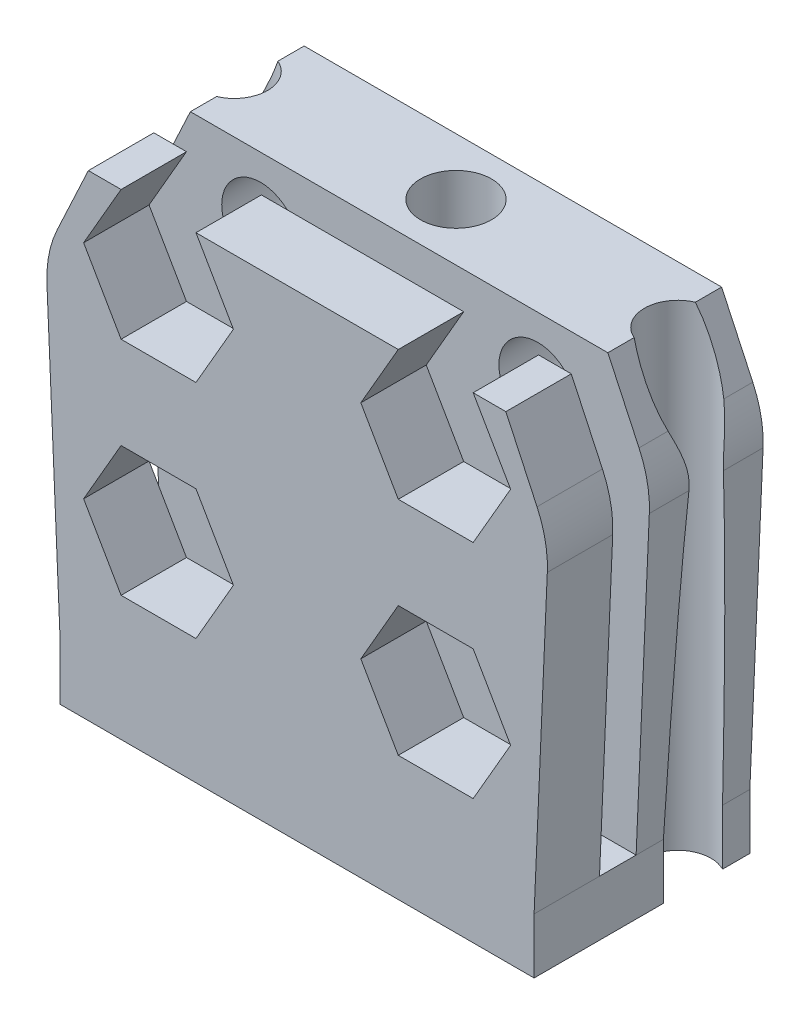
SolidWorks part; units mm, degrees
ref_plane "Front Plane" through (0, 0, 0) normal (0, 0, 1) x (1, 0, 0)
ref_plane "Top Plane" through (0, 0, 0) normal (0, 1, 0) x (1, 0, 0)
ref_plane "Right Plane" through (0, 0, 0) normal (1, 0, 0) x (0, 0, -1)
sketch "Sketch1" plane through (0, 0, 0) normal (0, 0, 1) x (1, 0, 0)
  line L0 (-10.6869, 72.9419) -> (10.6869, 72.9419)
  line L1 (-16.5368, 72.9419) -> (10.0115, 72.9419) construction
  line L9 (8.1815, 15.5604) -> (11.2824, 86.5808)
  line L10 (10.8187, 88.912) -> (7.7036, 95.5923)
  line L11 (-7.7036, 95.5923) -> (-10.8187, 88.912)
  line L12 (-11.2824, 86.5808) -> (-8.1815, 15.5604)
  line L13 (-12.9793, 4.4071) -> (-12.1223, -7.8488)
  line L14 (-11.0475, -10.6126) -> (-8.2635, -14.1126)
  line L15 (-4.3504, -16) -> (4.3504, -16)
  line L16 (8.2635, -14.1126) -> (11.0475, -10.6126)
  line L17 (12.1223, -7.8488) -> (12.9793, 4.4071)
  line L18 (8.1815, 15.5604) -> (11.2824, 86.5808)
  line L19 (10.8187, 88.912) -> (7.7036, 95.5923)
  line L20 (-7.7036, 95.5923) -> (-10.8187, 88.912)
  line L21 (-11.2824, 86.5808) -> (-8.1815, 15.5604)
  line L22 (-12.9793, 4.4071) -> (-12.1223, -7.8488)
  line L23 (-11.0475, -10.6126) -> (-8.2635, -14.1126)
  line L24 (-4.3504, -16) -> (4.3504, -16)
  line L25 (8.2635, -14.1126) -> (11.0475, -10.6126)
  line L26 (12.1223, -7.8488) -> (12.9793, 4.4071)
  circle A0 centre (6.25, 79) radius 1.5 construction
  circle A1 centre (6.25, 79) radius 1.5
  circle A2 centre (-6.25, 79) radius 1.5 construction
  circle A3 centre (-6.25, 79) radius 1.5
  circle A4 centre (-6.25, 89) radius 1.5 construction
  circle A5 centre (-6.25, 89) radius 1.5
  circle A6 centre (6.25, 89) radius 1.5 construction
  circle A7 centre (6.25, 89) radius 1.5
  arc A11 (8.1815, 15.5604) -> (9.9632, 11.5118) centre (13.1768, 15.3423) ccw
  arc A12 (11.2824, 86.5808) -> (10.8187, 88.912) centre (6.2871, 86.7989) ccw
  arc A13 (7.7036, 95.5923) -> (-7.7036, 95.5923) centre (0, 92) ccw
  arc A14 (-10.8187, 88.912) -> (-11.2824, 86.5808) centre (-6.2871, 86.7989) ccw
  arc A15 (-9.9632, 11.5118) -> (-8.1815, 15.5604) centre (-13.1768, 15.3423) ccw
  arc A16 (-9.9632, 11.5118) -> (-12.9793, 4.4071) centre (-4.5, 5) ccw
  arc A17 (-12.1223, -7.8488) -> (-11.0475, -10.6126) centre (-7.1345, -7.5) ccw
  arc A18 (-8.2635, -14.1126) -> (-4.3504, -16) centre (-4.3504, -11) ccw
  arc A19 (4.3504, -16) -> (8.2635, -14.1126) centre (4.3504, -11) ccw
  arc A20 (11.0475, -10.6126) -> (12.1223, -7.8488) centre (7.1345, -7.5) ccw
  arc A21 (12.9793, 4.4071) -> (9.9632, 11.5118) centre (4.5, 5) ccw
  arc A22 (8.1815, 15.5604) -> (9.9632, 11.5118) centre (13.1768, 15.3423) ccw
  arc A23 (11.2824, 86.5808) -> (10.8187, 88.912) centre (6.2871, 86.7989) ccw
  arc A24 (7.7036, 95.5923) -> (-7.7036, 95.5923) centre (0, 92) ccw
  arc A25 (-10.8187, 88.912) -> (-11.2824, 86.5808) centre (-6.2871, 86.7989) ccw
  arc A26 (-9.9632, 11.5118) -> (-8.1815, 15.5604) centre (-13.1768, 15.3423) ccw
  arc A27 (-9.9632, 11.5118) -> (-12.9793, 4.4071) centre (-4.5, 5) ccw
  arc A28 (-12.1223, -7.8488) -> (-11.0475, -10.6126) centre (-7.1345, -7.5) ccw
  arc A29 (-8.2635, -14.1126) -> (-4.3504, -16) centre (-4.3504, -11) ccw
  arc A30 (4.3504, -16) -> (8.2635, -14.1126) centre (4.3504, -11) ccw
  arc A31 (11.0475, -10.6126) -> (12.1223, -7.8488) centre (7.1345, -7.5) ccw
  arc A32 (12.9793, 4.4071) -> (9.9632, 11.5118) centre (4.5, 5) ccw
  dimension "D1" = 0
extrude "Boss-Extrude1" add sketch "Sketch1" along normal blind 5.13 contours L20 A25 L21 L0 L18 A23 L19 A24 A1 A3 A5 A7 region at (0, 85.3558, 0)
sketch "Sketch2" plane through (0, 72.9419, 0) normal (0, -1, 0) x (1, 0, 0)
  line L4 (-10.6869, 0) -> (10.6869, 0)
  line L5 (10.6869, 0) -> (10.6869, 5.13)
  line L6 (10.6869, 5.13) -> (-10.6869, 5.13)
  line L7 (-10.6869, 5.13) -> (-10.6869, 0)
  line L8 (-10.6869, 0) -> (10.6869, 0)
  line L9 (10.6869, 0) -> (10.6869, 5.13)
  line L10 (10.6869, 5.13) -> (-10.6869, 5.13)
  line L11 (-10.6869, 5.13) -> (-10.6869, 0)
  dimension "D1" = 0
extrude "Boss-Extrude2" add sketch "Sketch2" along normal blind 2.5
sketch "Sketch3" plane through (0, 0, 5.13) normal (0, 0, 1) x (1, 0, 0)
  line L1 (-10.6869, 72.9419) -> (10.6869, 72.9419)
  line L2 (-10.6869, 72.9419) -> (-10.6869, 70.4419)
  line L3 (-10.6869, 70.4419) -> (10.6869, 70.4419)
  line L4 (10.6869, 72.9419) -> (10.6869, 70.4419)
extrude "Boss-Extrude3" add sketch "Sketch3" along normal blind 4.6
sketch "Sketch4" plane through (0, 0, 9.73) normal (0, 0, 1) x (1, 0, 0)
  line L0 (-6.25, 89) -> (-2.8725, 89) construction
  line L1 (-2.8725, 89) -> (-4.5613, 91.925)
  line L2 (-4.5613, 91.925) -> (-7.9387, 91.925)
  line L3 (-7.9387, 91.925) -> (-9.6275, 89)
  line L4 (-9.6275, 89) -> (-7.9387, 86.075)
  line L5 (-10.6869, 72.9419) -> (10.6869, 72.9419)
  line L6 (10.6869, 72.9419) -> (11.2824, 86.5808)
  line L7 (10.8187, 88.912) -> (7.7036, 95.5923)
  line L8 (-7.7036, 95.5923) -> (-10.8187, 88.912)
  line L9 (-11.2824, 86.5808) -> (-10.6869, 72.9419)
  line L10 (-10.6869, 72.9419) -> (10.6869, 72.9419)
  line L11 (10.6869, 72.9419) -> (11.2824, 86.5808)
  line L12 (10.8187, 88.912) -> (7.7036, 95.5923)
  line L13 (-7.7036, 95.5923) -> (-10.8187, 88.912)
  line L14 (-11.2824, 86.5808) -> (-10.6869, 72.9419)
  line L15 (-7.9387, 86.075) -> (-4.5613, 86.075)
  line L16 (-4.5613, 86.075) -> (-2.8725, 89)
  line L17 (6.25, 89) -> (2.8725, 89) construction
  line L18 (2.8725, 89) -> (4.5613, 86.075)
  line L19 (4.5613, 86.075) -> (7.9387, 86.075)
  line L20 (7.9387, 86.075) -> (9.6275, 89)
  line L21 (9.6275, 89) -> (7.9387, 91.925)
  line L22 (7.9387, 91.925) -> (4.5613, 91.925)
  line L23 (4.5613, 91.925) -> (2.8725, 89)
  line L24 (-6.25, 79) -> (-2.8725, 79) construction
  line L25 (-2.8725, 79) -> (-4.5613, 81.925)
  line L26 (-4.5613, 81.925) -> (-7.9387, 81.925)
  line L27 (-7.9387, 81.925) -> (-9.6275, 79)
  line L28 (-9.6275, 79) -> (-7.9387, 76.075)
  line L29 (-7.9387, 76.075) -> (-4.5613, 76.075)
  line L30 (-4.5613, 76.075) -> (-2.8725, 79)
  line L31 (6.25, 79) -> (2.8725, 79) construction
  line L32 (9.6275, 79) -> (7.9387, 81.925)
  line L33 (7.9387, 81.925) -> (4.5613, 81.925)
  line L34 (4.5613, 81.925) -> (2.8725, 79)
  line L35 (2.8725, 79) -> (4.5613, 76.075)
  line L36 (4.5613, 76.075) -> (7.9387, 76.075)
  line L37 (7.9387, 76.075) -> (9.6275, 79)
  line L38 (9.6275, 89) -> (-9.6275, 89)
  line L39 (-9.6275, 89) -> (-10.7776, 89)
  line L40 (9.6275, 89) -> (10.7776, 89)
  line L41 (-4.5613, 91.925) -> (4.5613, 91.925)
  line L43 (7.9387, 91.925) -> (9.4137, 91.925)
  line L44 (-7.9387, 91.925) -> (-9.4137, 91.925)
  circle A0 centre (6.25, 89) radius 1.5 construction
  circle A1 centre (-6.25, 89) radius 1.5 construction
  circle A2 centre (-6.25, 79) radius 1.5 construction
  arc A3 (11.2824, 86.5808) -> (10.8187, 88.912) centre (6.2871, 86.7989) ccw
  arc A4 (7.7036, 95.5923) -> (-7.7036, 95.5923) centre (0, 92) ccw
  arc A5 (-10.8187, 88.912) -> (-11.2824, 86.5808) centre (-6.2871, 86.7989) ccw
  arc A6 (11.2824, 86.5808) -> (10.8187, 88.912) centre (6.2871, 86.7989) ccw
  arc A7 (7.7036, 95.5923) -> (-7.7036, 95.5923) centre (0, 92) ccw
  arc A8 (-10.8187, 88.912) -> (-11.2824, 86.5808) centre (-6.2871, 86.7989) ccw
  circle A9 centre (6.25, 79) radius 1.5 construction
  circle A10 centre (6.25, 89) radius 1.5
  circle A11 centre (-6.25, 89) radius 1.5
  circle A12 centre (-6.25, 79) radius 1.5
  circle A13 centre (6.25, 79) radius 1.5
  circle A14 centre (-6.25, 89) radius 2.925 construction
  circle A15 centre (6.25, 89) radius 2.925 construction
  circle A16 centre (-6.25, 79) radius 2.925 construction
  circle A17 centre (6.25, 79) radius 2.925 construction
  line M12 (10.6869, 72.9419) -> (-10.6869, 72.9419)
  dimension "D2" = 5.85
  dimension "D1" = 0
extrude "Boss-Extrude4" add sketch "Sketch4" against normal offset from surface (2.95 mm away) 1.65 contours L13 A8 L14 L11 A6 L12 A7 L16 L15 L4 L3 L2 L1 L23 L22 L21 L20 L19 L18 L30 L29 L28 L27 L26 L25 L37 L36 L35 L34 L33 L32 M12 | L1 L38 L23 L22 L21 L40 L12 | L43 L21 L40 L12 | L3 L44 L13 L39 region at (0, 80.7455, 9.73) region at (0, 90.5732, 9.73) region at (-9.4079, 90.5228, 9.73) region at (9.4079, 90.5228, 9.73) up to face at (0, 86.6272, 5.13)
sketch "Sketch5" plane through (0, 0, 0) normal (0, 0, -1) x (-1, 0, 0)
  circle A0 centre (-6.25, 89) radius 1.75
  circle A1 centre (6.25, 89) radius 1.75
  circle A2 centre (6.25, 79) radius 1.75
  circle A3 centre (-6.25, 79) radius 1.75
  dimension "D1" = 3.5
extrude "Cut-Extrude1" cut sketch "Sketch5" against normal up to next
sketch "Sketch6" plane through (0, 70.4419, 0) normal (0, -1, 0) x (1, 0, 0)
  line L0 (-10.6869, 2.565) -> (10.6869, 2.565) construction
  line L1 (-10.6869, 9.73) -> (-10.6869, 0) construction
  line L2 (10.6869, 0) -> (10.6869, 9.73) construction
  line L3 (-10.6869, 5.13) -> (-10.6869, 0) construction
  line L4 (0, 0) -> (0, 9.73) construction
  line L5 (-10.6869, 9.73) -> (10.6869, 9.73) construction
  circle A0 centre (0, 2.565) radius 1.6
  circle A1 centre (-10, 2.565) radius 1.5
  circle A2 centre (10, 2.565) radius 1.5
  dimension "D1" = 3.2
  dimension "D3" = 3
  dimension "D2" = 10
extrude "Cut-Extrude2" cut sketch "Sketch6" against normal through all
sketch "Sketch7" plane through (0, 0, 5.13) normal (0, 0, 1) x (1, 0, 0)
  line L0 (-9.4137, 91.925) -> (9.4137, 91.925)
  line L1 (-6.25, 89) -> (-4.5, 89) construction
  line L2 (-4.5613, 91.925) -> (4.5613, 91.925) construction
  line L5 (-10.6869, 72.9419) -> (10.6869, 72.9419)
  line L6 (10.6869, 72.9419) -> (11.2824, 86.5808)
  line L7 (10.8187, 88.912) -> (7.7036, 95.5923)
  line L8 (-7.7036, 95.5923) -> (-10.8187, 88.912)
  line L9 (-11.2824, 86.5808) -> (-10.6869, 72.9419)
  line L10 (-10.6869, 72.9419) -> (10.6869, 72.9419)
  line L11 (10.6869, 72.9419) -> (11.2824, 86.5808)
  line L12 (10.8187, 88.912) -> (7.7036, 95.5923)
  line L13 (-7.7036, 95.5923) -> (-10.8187, 88.912)
  line L14 (-11.2824, 86.5808) -> (-10.6869, 72.9419)
  circle A0 centre (-6.25, 89) radius 1.75 construction
  arc A3 (11.2824, 86.5808) -> (10.8187, 88.912) centre (6.2871, 86.7989) ccw
  arc A4 (7.7036, 95.5923) -> (-7.7036, 95.5923) centre (0, 92) ccw
  arc A5 (-10.8187, 88.912) -> (-11.2824, 86.5808) centre (-6.2871, 86.7989) ccw
  arc A6 (11.2824, 86.5808) -> (10.8187, 88.912) centre (6.2871, 86.7989) ccw
  arc A7 (7.7036, 95.5923) -> (-7.7036, 95.5923) centre (0, 92) ccw
  arc A8 (-10.8187, 88.912) -> (-11.2824, 86.5808) centre (-6.2871, 86.7989) ccw
  line M16 (10.8187, 88.912) -> (7.7036, 95.5923)
  arc M17 (7.7036, 95.5923) -> (-7.7036, 95.5923) centre (0, 92) ccw
  line M18 (-7.7036, 95.5923) -> (-10.8187, 88.912)
  dimension "D1" = 0
extrude "Cut-Extrude3" cut sketch "Sketch7" against normal up to next contours L0 M18 M16 M17 region at (0, 95.5138, 5.13)
